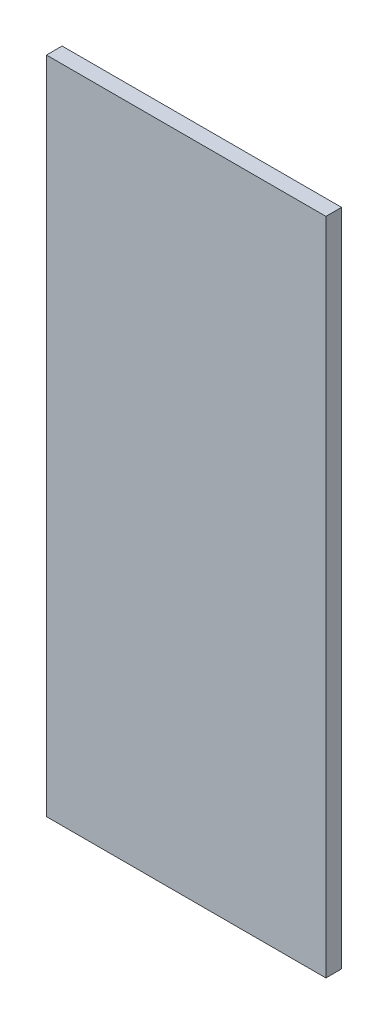
SolidWorks part; units mm, degrees
material "Perspex (TM) GS Acrylic Cast Sheet"
ref_plane "Front Plane" through (0, 0, 0) normal (0, 0, 1) x (1, 0, 0)
ref_plane "Top Plane" through (0, 0, 0) normal (0, 1, 0) x (1, 0, 0)
ref_plane "Right Plane" through (0, 0, 0) normal (1, 0, 0) x (0, 0, -1)
sketch "Sketch1" plane through (0, 0, 0) normal (0, 0, 1) x (1, 0, 0)
  line L1 (-80.5, -190) -> (80.5, -190)
  line L2 (-80.5, -190) -> (-80.5, 190)
  line L3 (-80.5, 190) -> (80.5, 190)
  line L4 (80.5, -190) -> (80.5, 190)
  line L5 (-80.5, -190) -> (80.5, 190) construction
  line L6 (-80.5, 190) -> (80.5, -190) construction
  point P0 (0, 0)
  dimension "D1" = 161
  dimension "D2" = 380
extrude "Boss-Extrude1" add sketch "Sketch1" along normal blind 9
equation "\"PCLength\"= 143mm'Length across I/O from PS to GPU"
equation "\"PCWidth\"= 340mm'Distance of longest part parallel to GPU(ussually GPU)"
equation "\"PCHeight\"= 190mm'Tallest point with mobo laying flat"
equation "\"WallThickness\"= 9mm'Thickness of each outer tank wall"
equation "\"ThermoBarrierThickness\"= 6mm'Thickness of barrier between hot side and cold side"
equation "\"HotSideGap\"= 15mm'Space in the hot side that hot fluid flows into"
equation "\"PCClearance\"= 40mm'Clearance from top of tank to top of PC"
equation "\"RadiatorHeight\"= 277.37mm'Final Height from ground of radiators"
equation "\"D1@Sketch1\"=\"PCLength\" + (2 * \"WallThickness\")"
equation "\"D2@Sketch1\"=\"PCWidth\" + \"PCClearance\""
equation "\"D1@Boss-Extrude1\"=\"WallThickness\""
